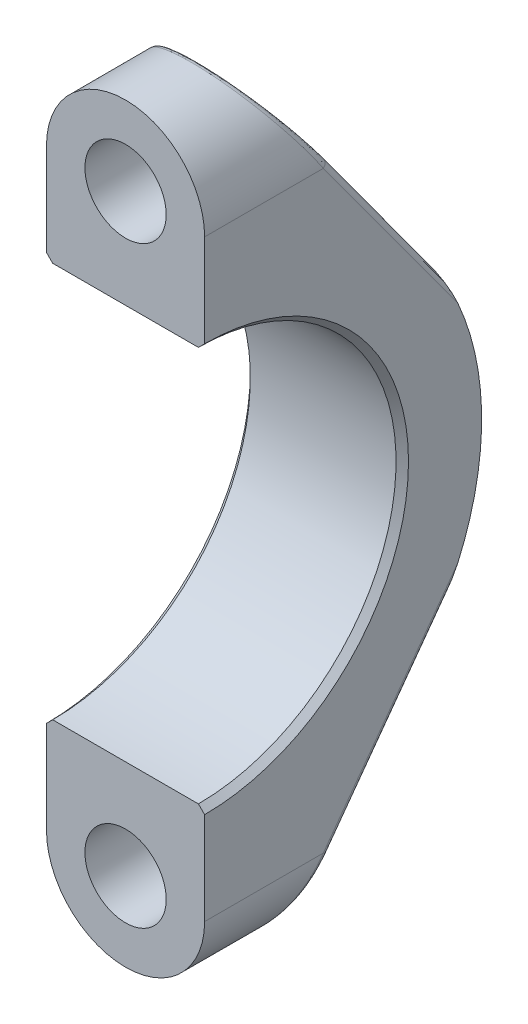
SolidWorks part; units mm, degrees
ref_plane "Front Plane" through (0, 0, 0) normal (0, 0, 1) x (1, 0, 0)
ref_plane "Top Plane" through (0, 0, 0) normal (0, 1, 0) x (1, 0, 0)
ref_plane "Right Plane" through (0, 0, 0) normal (1, 0, 0) x (0, 0, -1)
sketch "Sketch2" plane through (0, 0, 0) normal (0, 0, 1) x (1, 0, 0)
  line L2 (-6.35, 23.8125) -> (-6.35, -23.8114)
  line L4 (6.35, 23.8125) -> (6.35, -23.8114)
  arc A0 (-6.35, -23.8114) -> (6.35, -23.8114) centre (0, -23.8114) ccw
  arc A1 (6.35, 23.8125) -> (-6.35, 23.8125) centre (0, 23.8125) ccw
  circle A2 centre (0, -23.8114) radius 3.2639
  circle A3 centre (0, 23.8125) radius 3.2639
  point P0 (0, 0)
  point P6 (0, -23.8114)
  point P10 (0, 0)
  point P12 (0, 0)
  point P13 (0, -23.8114)
  point P14 (0, -23.8114)
  dimension "D3" = 12.7
  dimension "D1" = 6.5278
  dimension "D4" = 6.5278
  dimension "D2" = 12.7
extrude "Boss-Extrude1" add sketch "Sketch2" along normal blind 25.0031
sketch "Sketch4" plane through (6.35, 0, 0) normal (1, 0, 0) x (0, 0, -1)
  line L0 (-25.0031, -23.8114) -> (-25.0031, 23.8125) construction
  circle A0 centre (-25.0031, 0.0005) radius 15.875
  dimension "D1" = 31.75
extrude "Cut-Extrude2" cut sketch "Sketch4" against normal through all
sketch "Sketch5" plane through (6.35, 0, 0) normal (1, 0, 0) x (0, 0, -1)
  line L0 (-25.0031, 30.1625) -> (-19.4924, 30.1625)
  line L1 (0, 30.1625) -> (-25.0031, 30.1625) construction
  line L2 (-19.4924, 30.1625) -> (-6.7665, 12.7477)
  line L4 (-19.4924, 30.1625) -> (13.2932, 44.5308)
  line L5 (-19.4924, -30.1614) -> (-6.7665, -12.7466)
  line L6 (13.2932, 44.5308) -> (11.4726, -44.3877)
  line L7 (11.4726, -44.3877) -> (-19.4924, -30.1614)
  arc A0 (-6.7665, -12.7466) -> (-6.7665, 12.7477) centre (-25.0031, 0.0005) ccw
  dimension "D4" = 44.5
  dimension "D1" = 5.5107
  dimension "D3" = 17.4148
extrude "Cut-Extrude3" cut sketch "Sketch5" against normal through all contours L7 L6 L4 L2 A0 L5 | A0 L5 L6 L7 L2
chamfer "Chamfer3" distance 0.5 angle 45 2 edges at (-6.35, 0.0005, 9.1281) (6.35, 0.0005, 9.1281)
fillet "Fillet1" radius 0.5 8 edges at (0, 30.1625, 19.4924) (-6.35, 18.2801, 10.8093) (6.35, 18.2801, 10.8093) (0, 20.5486, 12.467) (-6.35, -18.279, 10.8093) (6.35, -18.279, 10.8093) (0, -30.1614, 19.4924) (0, -20.5475, 12.467)
